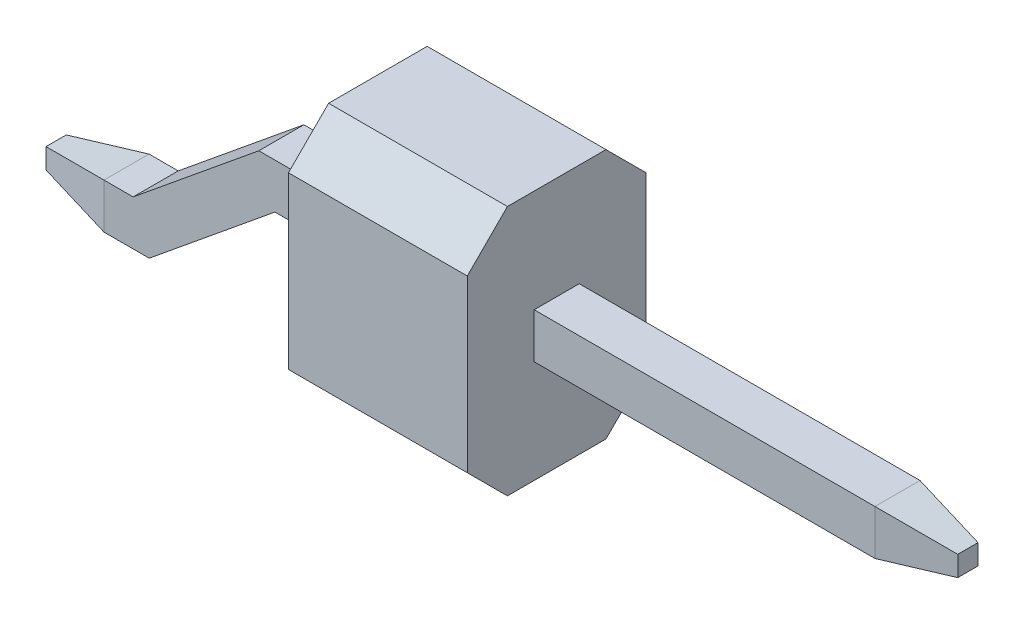
SolidWorks part; units mm, degrees
ref_plane "Front Plane" through (0, 0, 0) normal (0, 0, 1) x (1, 0, 0)
ref_plane "Top Plane" through (0, 0, 0) normal (0, 1, 0) x (1, 0, 0)
ref_plane "Right Plane" through (0, 0, 0) normal (1, 0, 0) x (0, 0, -1)
sketch "Sketch1" plane through (0, 0, 0) normal (0, 1, 0) x (1, 0, 0)
  line L1 (0, 0) -> (2.54, 0)
  line L2 (0, 0) -> (0, 2.54)
  line L3 (0, 2.54) -> (2.54, 2.54)
  line L4 (2.54, 0) -> (2.54, 2.54)
  dimension "D1" = 2.54
  dimension "D2" = 2.54
extrude "Boss-Extrude1" add sketch "Sketch1" along normal blind 3.56
sketch "Sketch2" plane through (2.54, 0, 0) normal (1, 0, 0) x (0, 0, -1)
  line L1 (0.95, 2.1) -> (1.59, 2.1)
  line L2 (0.95, 2.1) -> (0.95, 1.46)
  line L3 (0.95, 1.46) -> (1.59, 1.46)
  line L4 (1.59, 2.1) -> (1.59, 1.46)
  line L5 (1.27, 2.1) -> (1.27, 3.56) construction
  line L6 (0, 3.56) -> (2.54, 3.56) construction
  line L7 (0.95, 1.78) -> (0, 1.78) construction
  line L8 (0, 3.56) -> (0, 0) construction
  line L9 (0, 0) -> (2.54, 0)
  line L10 (2.54, 0) -> (2.54, 3.56)
  line L11 (2.54, 3.56) -> (0, 3.56)
  line L12 (0, 3.56) -> (0, 0)
  line L13 (0, 0) -> (2.54, 0) construction
  line L14 (2.54, 0) -> (2.54, 3.56) construction
  line L15 (2.54, 3.56) -> (0, 3.56) construction
  line L16 (0, 3.56) -> (0, 0) construction
  dimension "D2" = 0.64
  dimension "D1" = 0
extrude "Boss-Extrude2" add sketch "Sketch2" along normal blind 5.84
chamfer "Chamfer1" distance 0.57 angle 45 4 edges at (1.27, 0, -2.54) (1.27, 0, 0) (1.27, 3.56, -2.54) (1.27, 3.56, 0)
chamfer "Chamfer2" distance 1 angle 10 4 edges at (8.38, 2.1, -1.27) (8.38, 1.78, -1.59) (8.38, 1.46, -1.27) (8.38, 1.78, -0.95) first distance on face at (5.46, 2.1, -1.27) first distance on face at (5.46, 1.78, -1.59) first distance on face at (5.46, 1.46, -1.27) first distance on face at (5.46, 1.78, -0.95)
sketch "Sketch3" plane through (0, 0, 0) normal (-1, 0, 0) x (0, 0, 1)
  line L0 (-0.95, 2.1) -> (-0.95, 1.46) construction
  line L1 (-0.95, 1.46) -> (-1.59, 1.46) construction
  line L2 (-1.59, 2.1) -> (-0.95, 2.1) construction
  line L3 (-1.59, 1.46) -> (-1.59, 2.1) construction
  line L4 (-0.95, 2.1) -> (-0.95, 1.46)
  line L5 (-0.95, 1.46) -> (-1.59, 1.46)
  line L6 (-1.59, 2.1) -> (-0.95, 2.1)
  line L7 (-1.59, 1.46) -> (-1.59, 2.1)
extrude "Boss-Extrude3" add sketch "Sketch3" along normal blind 2.285
sketch "Sketch4" plane through (-2.285, 0, 0) normal (-1, 0, 0) x (0, 0, 1)
  line L1 (-1.59, 1.46) -> (-0.95, 1.46) construction
  line L2 (-0.95, 0) -> (-1.59, 0)
  line L3 (-0.95, 0) -> (-0.95, 0.64)
  line L4 (-0.95, 0.64) -> (-1.59, 0.64)
  line L5 (-1.59, 0) -> (-1.59, 0.64)
  line L6 (-1.59, 2.1) -> (-1.59, 1.46) construction
  line L7 (-1.97, 0) -> (-0.57, 0) construction
extrude "Boss-Extrude4" add sketch "Sketch4" along normal blind 2.285 separate body
chamfer "Chamfer3" distance 1 angle 10 4 edges at (-4.57, 0, -1.27) (-4.57, 0.32, -1.59) (-4.57, 0.64, -1.27) (-4.57, 0.32, -0.95) first distance on face at (-3.4275, 0, -1.27) first distance on face at (-3.4275, 0.32, -1.59) first distance on face at (-3.4275, 0.64, -1.27) first distance on face at (-3.4275, 0.32, -0.95)
sketch "Sketch5" plane through (0, 0, -1.59) normal (0, 0, -1) x (-1, 0, 0)
  line L1 (2.285, 0.5255) -> (1.1425, 1.46)
  line L2 (2.285, 1.46) -> (0, 1.46) construction
  line L3 (3.1559, 0.64) -> (2.1534, 1.46)
  line L4 (3.3327, 0.4954) -> (1.5477, 1.9554) construction
  line L5 (3.57, 0.64) -> (2.285, 0.64) construction
  line L6 (1.1425, 1.46) -> (2.1534, 1.46)
  line L7 (2.285, 0.64) -> (3.1559, 0.64)
  line L8 (2.285, 0.64) -> (2.285, 0.5255)
  line L9 (2.285, 0.64) -> (2.285, 0) construction
  line L10 (2.285, 0.5255) -> (2.9275, 0) construction
  line L11 (2.9275, 0) -> (1.1425, 1.46) construction
  line L12 (3.57, 0) -> (2.285, 0) construction
  dimension "D1" = 0.64
extrude "Boss-Extrude5" add sketch "Sketch5" against normal up to surface (0.64 mm away) up to face at (-1.1425, 1.78, -0.95)
sketch "Sketch6" plane through (0, 0, -1.59) normal (0, 0, -1) x (-1, 0, 0)
  line L0 (3.1559, 0.64) -> (2.1534, 1.46) construction
  line L1 (2.1534, 1.46) -> (1.3709, 2.1)
  line L2 (2.285, 2.1) -> (0, 2.1) construction
  line L3 (2.285, 2.1) -> (2.285, 1.46) construction
  line L4 (2.285, 1.46) -> (2.1534, 1.46) construction
  line L5 (2.285, 2.1) -> (2.285, 1.46)
  line L6 (2.285, 1.46) -> (2.1534, 1.46)
  line L7 (1.3709, 2.1) -> (2.285, 2.1)
  line L8 (1.1425, 1.46) -> (2.285, 0.5255) construction
  line L9 (2.285, 0.5255) -> (2.9275, 0)
  line L10 (3.57, 0) -> (2.285, 0) construction
  line L11 (2.285, 0.5255) -> (2.285, 0) construction
  line L12 (2.285, 0.5255) -> (2.285, 0)
  line L13 (2.285, 0) -> (2.9275, 0)
extrude "Cut-Extrude1" cut sketch "Sketch6" against normal through all both and the other way through all
